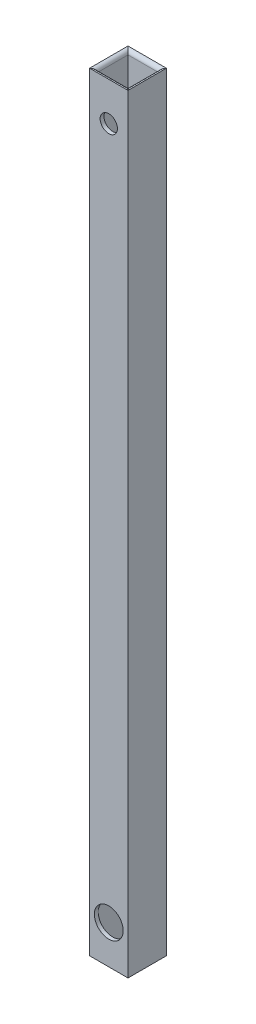
SolidWorks part; units mm, degrees
ref_plane "Front Plane" through (0, 0, 0) normal (0, 0, 1) x (1, 0, 0)
ref_plane "Top Plane" through (0, 0, 0) normal (0, 1, 0) x (1, 0, 0)
ref_plane "Right Plane" through (0, 0, 0) normal (1, 0, 0) x (0, 0, -1)
sketch "Sketch1" plane through (0, 0, 0) normal (0, 1, 0) x (1, 0, 0)
  line L1 (-5, 5) -> (5, 5)
  line L2 (-5, 5) -> (-5, -5)
  line L3 (-5, -5) -> (5, -5)
  line L4 (5, 5) -> (5, -5)
  line L5 (-5, 5) -> (5, -5) construction
  line L6 (-5, -5) -> (5, 5) construction
  line L7 (-4, 4) -> (4, 4)
  line L8 (-4, 4) -> (-4, -4)
  line L9 (-4, -4) -> (4, -4)
  line L10 (4, 4) -> (4, -4)
  line L11 (-4, 4) -> (4, -4) construction
  line L12 (-4, -4) -> (4, 4) construction
  point P0 (0, 0)
  point P6 (0, 0)
  dimension "D1" = 10
  dimension "D2" = 10
  dimension "D3" = 8
extrude "Boss-Extrude1" add sketch "Sketch1" along normal blind 200
fillet "Fillet2" radius 1 8 edges at (4, 200, 0) (0, 200, -4) (-4, 200, 0) (0, 200, 4) (-4, 0, 0) (0, 0, 4) (4, 0, 0) (0, 0, -4)
sketch "Sketch2" plane through (0, 0, 5) normal (0, 0, 1) x (1, 0, 0)
  line L0 (5, 200) -> (5, 0) construction
  line L2 (-5, 0) -> (5, 0) construction
  circle A0 centre (0, 10) radius 3.75
  circle A1 centre (0, 190) radius 2.25
  dimension "D1" = 7.5
  dimension "D2" = 4.5
  dimension "D3" = 5
  dimension "D4" = 190
  dimension "D5" = 5
  dimension "D6" = 10
extrude "Cut-Extrude1" cut sketch "Sketch2" against normal through all
